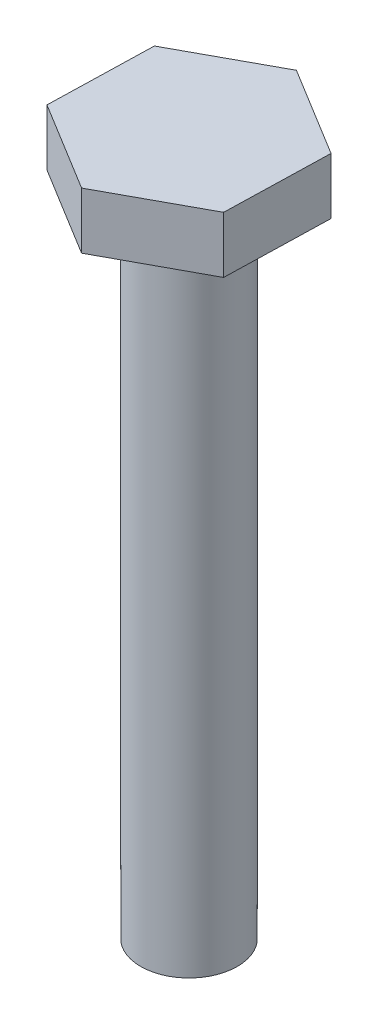
SolidWorks part; units mm, degrees
ref_plane "Front Plane" through (0, 0, 0) normal (0, 0, 1) x (1, 0, 0)
ref_plane "Top Plane" through (0, 0, 0) normal (0, 1, 0) x (1, 0, 0)
ref_plane "Right Plane" through (0, 0, 0) normal (1, 0, 0) x (0, 0, -1)
sketch "Sketch1" plane through (0, 0, 0) normal (0, 1, 0) x (1, 0, 0)
  line L1 (5.5434, -3.3943) -> (5.7112, 3.1035)
  line L2 (5.7112, 3.1035) -> (0.1679, 6.4978)
  line L3 (0.1679, 6.4978) -> (-5.5434, 3.3943)
  line L4 (-5.5434, 3.3943) -> (-5.7112, -3.1035)
  line L5 (-5.7112, -3.1035) -> (-0.1679, -6.4978)
  line L6 (-0.1679, -6.4978) -> (5.5434, -3.3943)
  circle A0 centre (0, 0) radius 5.6292 construction
extrude "Boss-Extrude1" add sketch "Sketch1" along normal blind 3.5
sketch "Sketch2" plane through (0, 0, 0) normal (0, -1, 0) x (1, 0, 0)
  circle A0 centre (0, 0) radius 3
extrude "Boss-Extrude2" add sketch "Sketch2" along normal blind 40
move or copy body "Body-Move/Copy1" [suppressed] bodies to move or copy 102
